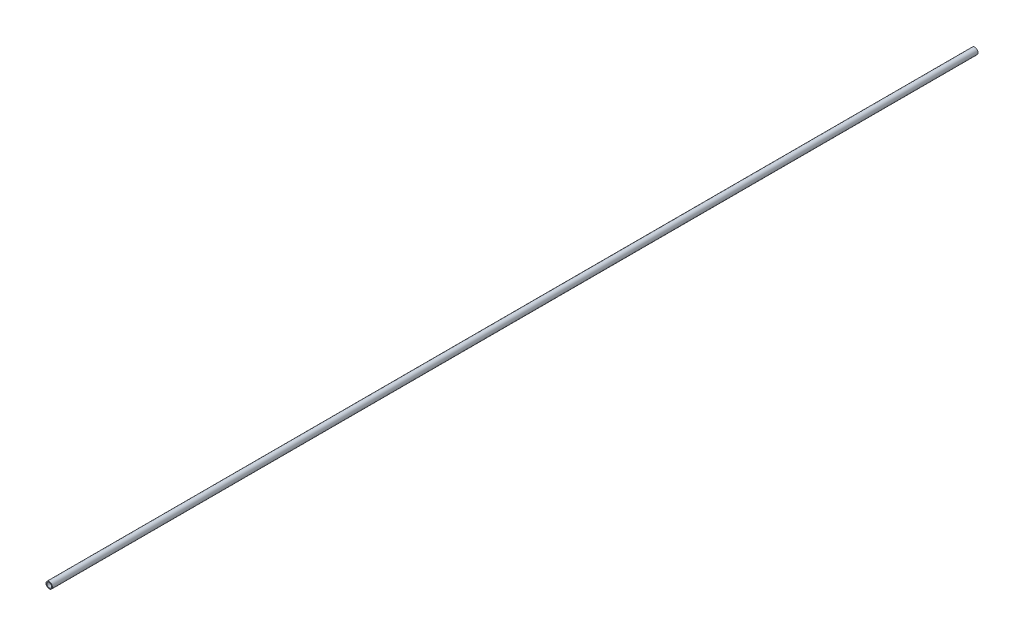
SolidWorks part; units mm, degrees
ref_plane "Front Plane" through (0, 0, 0) normal (0, 0, 1) x (1, 0, 0)
ref_plane "Top Plane" through (0, 0, 0) normal (0, 1, 0) x (1, 0, 0)
ref_plane "Right Plane" through (0, 0, 0) normal (1, 0, 0) x (0, 0, -1)
sketch "Sketch1" plane through (0, 0, 0) normal (0, 0, 1) x (1, 0, 0)
  circle A0 centre (0, 0) radius 6.35
  circle A1 centre (0, 0) radius 4.7625
  dimension "D1" = 12.7
  dimension "D2" = 9.525
extrude "Boss-Extrude1" add sketch "Sketch1" along normal blind 1828.8
